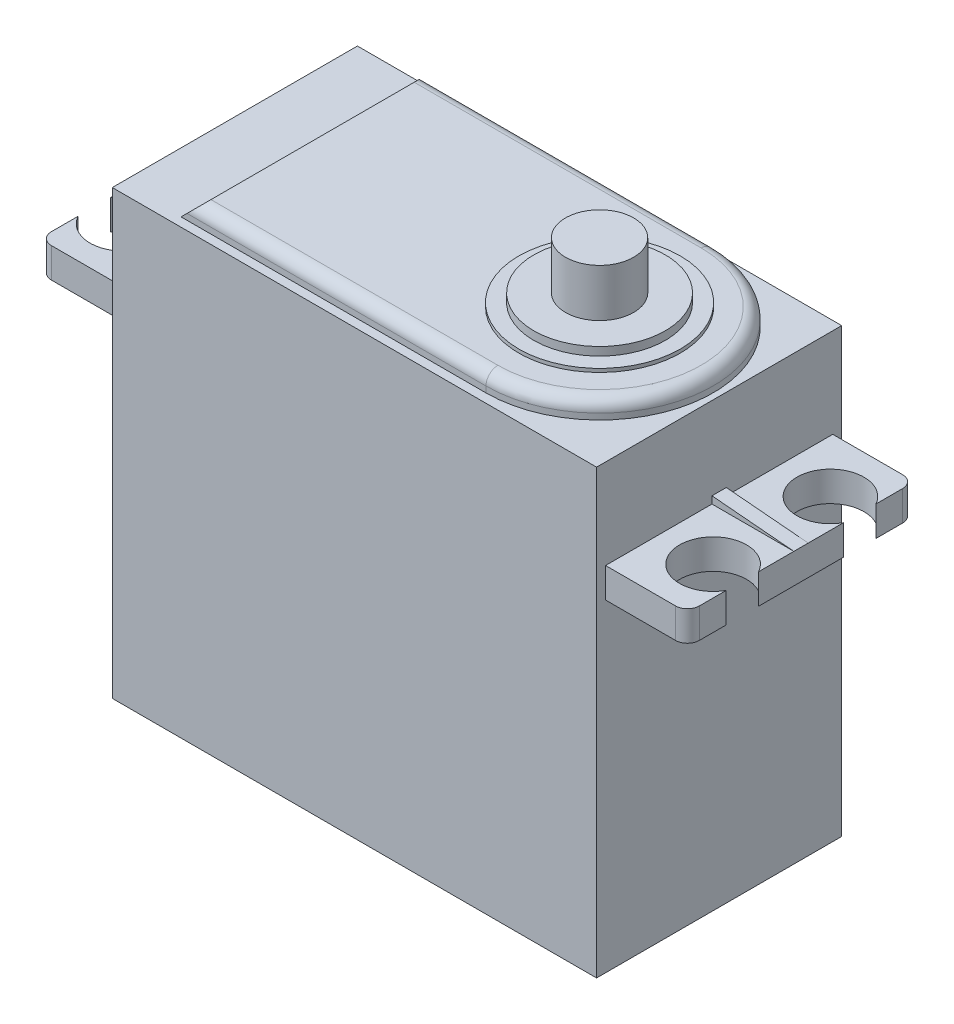
SolidWorks part; units mm, degrees
ref_plane "Alzado" through (0, 0, 0) normal (0, 0, 1) x (1, 0, 0)
ref_plane "Planta" through (0, 0, 0) normal (0, 1, 0) x (1, 0, 0)
ref_plane "Vista lateral" through (0, 0, 0) normal (1, 0, 0) x (0, 0, -1)
sketch "Croquis1" plane through (0, 0, 0) normal (0, 1, 0) x (1, 0, 0)
  line L1 (-20.25, -10.25) -> (20.25, -10.25)
  line L2 (-20.25, -10.25) -> (-20.25, 10.25)
  line L3 (-20.25, 10.25) -> (20.25, 10.25)
  line L4 (20.25, -10.25) -> (20.25, 10.25)
  line L5 (-20.25, -10.25) -> (20.25, 10.25) construction
  line L6 (-20.25, 10.25) -> (20.25, -10.25) construction
  point P0 (0, 0)
  dimension "D1" = 20.5
  dimension "D2" = 40.5
extrude "Saliente-Extruir1" add sketch "Croquis1" along normal blind 38.5
sketch "Croquis2" plane through (0, 38.5, 0) normal (0, 1, 0) x (1, 0, 0)
  line L0 (-20.25, 9.5) -> (-26.1, 9.5)
  line L1 (-20.25, 10.25) -> (-20.25, -10.25) construction
  line L2 (-27.1, 8.5) -> (-27.1, 6.2611)
  line L5 (-27.1, 3.55) -> (-27.1, 0)
  line L6 (-27.1, 0) -> (-20.25, 0)
  line L7 (-1000, 0) -> (49000, 0) construction
  line L8 (0, -1000) -> (0, 49000) construction
  line L9 (20.25, 10.25) -> (-20.25, 10.25) construction
  line L10 (-20.25, 0) -> (-20.25, 9.5)
  arc A0 (-27.1, 6.2611) -> (-27.1, 3.55) centre (-24.65, 4.9055) cw
  arc A1 (-26.1, 9.5) -> (-27.1, 8.5) centre (-26.1, 8.5) ccw
  dimension "D1" = 1
  dimension "D2" = 7.1
  dimension "D3" = 49.3
  dimension "D6" = 2.8
  dimension "D4" = 54.2
  dimension "D5" = 0.75
extrude "Saliente-Extruir2" add sketch "Croquis2" along normal blind 2.5 from offset 11.5 offset against normal yes
ref_plane "Plano1" through (0, 0, 0) normal (0, 0, -1) x (-1, 0, 0)
mirror "Simetría1" about plane through (0, 0, 0) normal (0, 0, -1) of "Saliente-Extruir2"
ref_plane "Plano3" through (0, 0, 0) normal (1, 0, 0) x (0, 0, -1)
ref_plane "Plano4" through (0, 0, 0) normal (0, 0, 1) x (1, 0, 0)
sketch "Croquis8" plane through (0, 0, 0) normal (0, 0, 1) x (1, 0, 0)
  line L0 (-27.1, 29.5) -> (-20.25, 30.0993)
  line L1 (-20.25, 38.5) -> (-20.25, 0) construction
  line L2 (-20.25, 30.0993) -> (-20.25, 29.5)
  line L3 (-20.25, 29.5) -> (-27.1, 29.5)
  dimension "D1" = 5
extrude "Saliente-Extruir6" add sketch "Croquis8" along normal mid plane 1.2
mirror "Simetría2" about plane through (0, 0, 0) normal (1, 0, 0) of "Saliente-Extruir6", "Saliente-Extruir2", "Simetría1"
sketch "Croquis4" plane through (0, 38.5, 0) normal (0, 1, 0) x (1, 0, 0)
  line L0 (-15.25, 9.5) -> (-15.25, -9.5)
  line L1 (-15.25, -9.5) -> (10.25, -9.5)
  line L2 (10.25, 9.5) -> (-15.25, 9.5)
  line L3 (0, 0) -> (10.25, 0) construction
  line L9 (20.25, -10.25) -> (20.25, 10.25)
  line L10 (20.25, 10.25) -> (-20.25, 10.25)
  line L11 (-20.25, 10.25) -> (-20.25, -10.25)
  line L12 (-20.25, -10.25) -> (20.25, -10.25)
  line L13 (20.25, -10.25) -> (20.25, 10.25)
  line L14 (20.25, 10.25) -> (-20.25, 10.25)
  line L15 (-20.25, 10.25) -> (-20.25, -10.25)
  line L16 (-20.25, -10.25) -> (20.25, -10.25)
  arc A0 (10.25, -9.5) -> (10.25, 9.5) centre (10.25, 0) ccw
  dimension "D2" = 35
  dimension "D4" = 0.5
  dimension "D1" = 19
  dimension "D3" = 0
extrude "Cortar-Extruir3" cut sketch "Croquis4" against normal blind 1.5
chamfer "Chaflán1" distance 1.5 angle 45 1 edges at (-15.25, 38.5, 0)
fillet "Redondeo1" radius 1 3 edges at (-1.75, 38.5, -9.5) (19.75, 38.5, 0) (-1.75, 38.5, 9.5)
sketch "Croquis5" plane through (0, 38.5, 0) normal (0, 1, 0) x (1, 0, 0)
  line L0 (-1000, 0) -> (49000, 0) construction
  circle A0 centre (10.25, 0) radius 6.75
  arc A1 (10.25, -8.5) -> (10.25, 8.5) centre (10.25, 0) ccw construction
  dimension "D1" = 13.5
extrude "Saliente-Extruir3" add sketch "Croquis5" along normal blind 0.3
sketch "Croquis6" plane through (0, 38.8, 0) normal (0, 1, 0) x (1, 0, 0)
  circle A0 centre (10.25, 0) radius 5.5
  circle A1 centre (10.25, 0) radius 6.75 construction
  dimension "D1" = 11
extrude "Saliente-Extruir4" add sketch "Croquis6" along normal blind 0.7
sketch "Croquis7" plane through (0, 39.5, 0) normal (0, 1, 0) x (1, 0, 0)
  circle A0 centre (10.25, 0) radius 2.85
  dimension "D1" = 5.7
extrude "Saliente-Extruir5" add sketch "Croquis7" along normal blind 4
